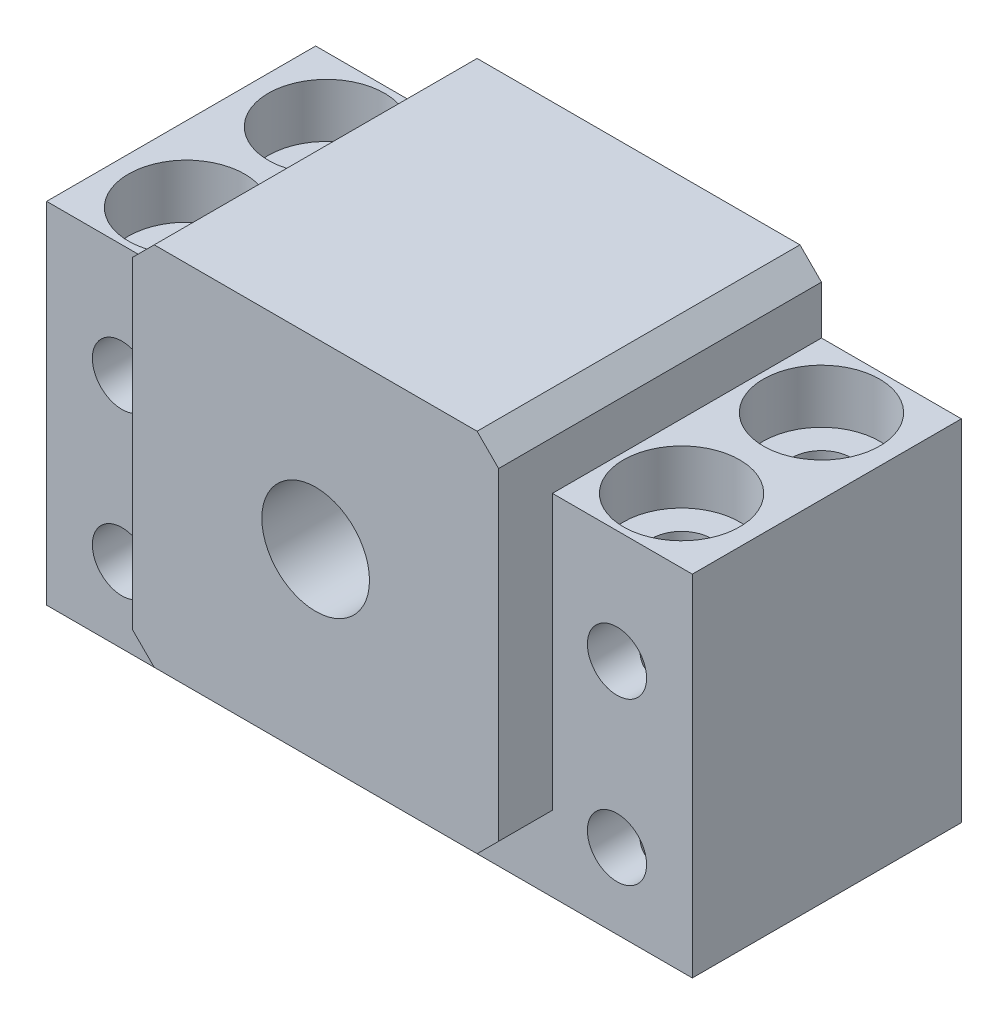
SolidWorks part; units mm, degrees
ref_plane "Front Plane" through (0, 0, 0) normal (0, 0, 1) x (1, 0, 0)
ref_plane "Top Plane" through (0, 0, 0) normal (0, 1, 0) x (1, 0, 0)
ref_plane "Right Plane" through (0, 0, 0) normal (1, 0, 0) x (0, 0, -1)
sketch "Sketch1" plane through (0, 0, 0) normal (0, 0, 1) x (1, 0, 0)
  line L0 (0, 0) -> (-17, 0) construction
  line L5 (0, 0) -> (0, 17) construction
  line L6 (15, 17) -> (-15, 17)
  line L7 (-15, 17) -> (-17, 15)
  line L8 (-17, 15) -> (-17, -15)
  line L9 (0, 0) -> (-17, 17) construction
  line L10 (-15, 17) -> (-17, 17) construction
  line L11 (-17, 15) -> (-17, 17) construction
  line L12 (17, 15) -> (17, 17) construction
  line L13 (15, 17) -> (17, 17) construction
  line L14 (0, 0) -> (17, 17) construction
  line L15 (17, 15) -> (17, -15)
  line L16 (15, 17) -> (17, 15)
  line L17 (15, -17) -> (17, -15)
  line L18 (-15, -17) -> (-17, -15)
  line L19 (15, -17) -> (-15, -17)
  circle A0 centre (0, 0) radius 5
  point P3 (-16, 16)
  point P19 (17, 0)
  dimension "D1" = 10
  dimension "D2" = 34
  dimension "D3" = 2
extrude "Boss-Extrude1" add sketch "Sketch1" along normal blind 5
sketch "Sketch2" plane through (0, 0, 0) normal (0, 0, -1) x (-1, 0, 0)
  line L0 (15, 17) -> (-15, 17)
  line L1 (-15, 17) -> (-17, 15)
  line L2 (-17, 15) -> (-17, 10.5)
  line L3 (-17, -15) -> (-17, 15) construction
  line L4 (-17, 10.5) -> (-30, 10.5)
  line L5 (-30, 10.5) -> (-30, -22)
  line L6 (-30, -22) -> (30, -22)
  line L7 (0, 17) -> (0, -22) construction
  line L8 (-23, 0) -> (-23, -15) construction
  line L9 (23, -15) -> (-23, -15) construction
  line L10 (0, 0) -> (-23, 0) construction
  line L11 (30, 10.5) -> (30, -22)
  line L12 (17, 10.5) -> (30, 10.5)
  line L13 (17, 15) -> (17, 10.5)
  line L14 (15, 17) -> (17, 15)
  circle A0 centre (0, 0) radius 5 construction
  circle A1 centre (0, 0) radius 5
  circle A2 centre (-23, 0) radius 2.75
  circle A3 centre (-23, -15) radius 2.75
  circle A4 centre (23, -15) radius 2.75
  circle A5 centre (23, 0) radius 2.75
  point P24 (0, -15)
  dimension "D3" = 5.5
  dimension "D1" = 32.5
  dimension "D2" = 39
  dimension "D4" = 60
  dimension "D5" = 46
  dimension "D6" = 15
extrude "Boss-Extrude2" add sketch "Sketch2" along normal blind 25
sketch "Sketch3" plane through (0, -22, 0) normal (0, -1, 0) x (1, 0, 0)
  line L0 (0, 0) -> (0, -25) construction
  line L1 (23, -19) -> (-23, -19) construction
  line L2 (23, -19) -> (23, -6) construction
  line L3 (23, -6) -> (-23, -6) construction
  line L4 (-23, -19) -> (-23, -6) construction
  line L5 (23, -19) -> (-23, -6) construction
  line L6 (23, -6) -> (-23, -19) construction
  line L7 (30, -25) -> (-30, -25) construction
  line L8 (-25.75, -6) -> (-25.75, 0) construction
  line L9 (-20.25, -6) -> (-20.25, 0) construction
  circle A0 centre (-23, -6) radius 2.75
  circle A1 centre (-23, -19) radius 2.75
  circle A2 centre (23, -6) radius 2.75
  circle A3 centre (23, -19) radius 2.75
  point P0 (0, -12.5)
  dimension "D1" = 13
  dimension "D2" = 6
extrude "Cut-Extrude1" cut sketch "Sketch3" against normal through all
sketch "Sketch4" plane through (0, 10.5, 0) normal (0, 1, 0) x (1, 0, 0)
  circle A0 centre (23, 6) radius 5.4
  circle A1 centre (23, 19) radius 5.4
  circle A2 centre (-23, 19) radius 5.4
  circle A3 centre (-23, 6) radius 5.4
  dimension "D1" = 10.8
extrude "Cut-Extrude2" cut sketch "Sketch4" against normal blind 5
